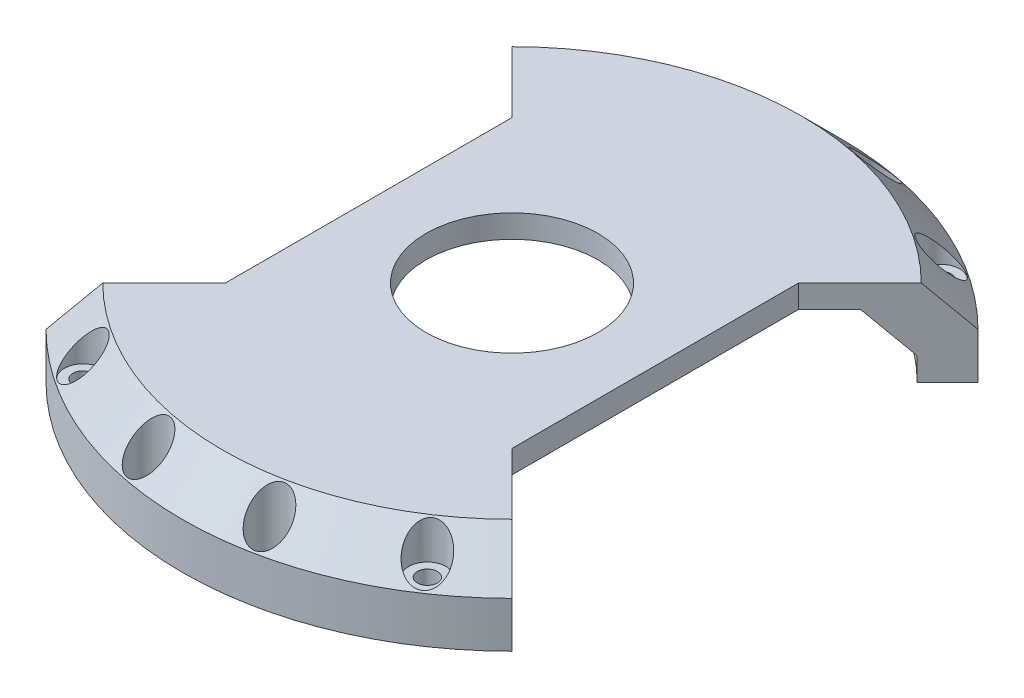
SolidWorks part; units mm, degrees
ref_plane "Front Plane" through (0, 0, 0) normal (0, 0, 1) x (1, 0, 0)
ref_plane "Top Plane" through (0, 0, 0) normal (0, 1, 0) x (1, 0, 0)
ref_plane "Right Plane" through (0, 0, 0) normal (1, 0, 0) x (0, 0, -1)
sketch "Sketch1" plane through (0, 0, 0) normal (0, 1, 0) x (1, 0, 0)
  circle A0 centre (0, 0) radius 57.5
  dimension "D1" = 115
extrude "Boss-Extrude1" add sketch "Sketch1" along normal blind 15
sketch "Sketch2" plane through (0, 0, 0) normal (0, -1, 0) x (1, 0, 0)
  circle A0 centre (0, 0) radius 50
  dimension "D1" = 100
extrude "Cut-Extrude1" cut sketch "Sketch2" against normal blind 11
sketch "Sketch3" plane through (0, 15, 0) normal (0, 1, 0) x (1, 0, 0)
  line L0 (0, 0) -> (0, 54) construction
  line L1 (0, 0) -> (-10.6273, 52.9439) construction
  circle A0 centre (0, 0) radius 54 construction
  circle A13 centre (0, 0) radius 15
  circle A14 centre (-10.6273, 52.9439) radius 1.75
  circle A15 centre (10.4424, 52.9807) radius 1.75
  circle A16 centre (29.9224, 44.9517) radius 1.75
  circle A17 centre (44.8469, 30.0791) radius 1.75
  circle A18 centre (52.9439, 10.6273) radius 1.75
  circle A19 centre (52.9807, -10.4424) radius 1.75
  circle A20 centre (44.9517, -29.9224) radius 1.75
  circle A21 centre (30.0791, -44.8469) radius 1.75
  circle A22 centre (10.6273, -52.9439) radius 1.75
  circle A23 centre (-10.4424, -52.9807) radius 1.75
  circle A24 centre (-29.9224, -44.9517) radius 1.75
  circle A25 centre (-44.8469, -30.0791) radius 1.75
  circle A26 centre (-52.9439, -10.6273) radius 1.75
  circle A27 centre (-52.9807, 10.4424) radius 1.75
  circle A28 centre (-44.9517, 29.9224) radius 1.75
  circle A29 centre (-30.0791, 44.8469) radius 1.75
  point P29 (0, 0)
  point P40 (0, 0)
  dimension "D1" = 108
  dimension "D2" = 11.35
  dimension "D4" = 30
  dimension "D3" = 3.5
extrude "Cut-Extrude2" cut sketch "Sketch3" against normal blind 15
sketch "Sketch4" plane through (0, 15, 0) normal (0, 1, 0) x (1, 0, 0)
  line L0 (25, 25) -> (40.6586, 40.6586)
  line L1 (-25, 25) -> (25, 25) construction
  line L2 (-25, 25) -> (-25, -25) construction
  line L3 (-25, -25) -> (25, -25) construction
  line L4 (25, 25) -> (25, -25)
  line L5 (-25, 25) -> (25, -25) construction
  line L6 (-25, -25) -> (25, 25) construction
  line L7 (25, -25) -> (40.6586, -40.6586)
  circle A0 centre (0, 0) radius 57.5 construction
  arc A1 (40.6586, -40.6586) -> (40.6586, 40.6586) centre (0, 0) ccw
  point P0 (0, 0)
  dimension "D1" = 50
extrude "Cut-Extrude3" cut sketch "Sketch4" against normal blind 15
mirror "Mirror1" about plane through (0, 0, 0) normal (1, 0, 0) of "Cut-Extrude3"
chamfer "Chamfer1" distance 7 angle 45 4 edges at (0, 15, -57.5) (0, 15, 57.5) (0, 11, 50) (0, 11, -50)
sketch "Sketch5" plane through (0, 15, 0) normal (0, 1, 0) x (1, 0, 0)
  line L0 (0, 0) -> (-10.6273, 52.9439) construction
  circle A0 centre (0, 0) radius 54 construction
  circle A1 centre (-10.6273, 52.9439) radius 3.25
  circle A2 centre (10.4424, 52.9807) radius 3.25
  circle A3 centre (29.9224, 44.9517) radius 3.25
  circle A4 centre (44.8469, 30.0791) radius 3.25
  circle A5 centre (52.9439, 10.6273) radius 3.25
  circle A6 centre (52.9807, -10.4424) radius 3.25
  circle A7 centre (44.9517, -29.9224) radius 3.25
  circle A8 centre (30.0791, -44.8469) radius 3.25
  circle A9 centre (10.6273, -52.9439) radius 3.25
  circle A10 centre (-10.4424, -52.9807) radius 3.25
  circle A11 centre (-29.9224, -44.9517) radius 3.25
  circle A12 centre (-44.8469, -30.0791) radius 3.25
  circle A13 centre (-52.9439, -10.6273) radius 3.25
  circle A14 centre (-52.9807, 10.4424) radius 3.25
  circle A15 centre (-44.9517, 29.9224) radius 3.25
  circle A16 centre (-30.0791, 44.8469) radius 3.25
  point P32 (0, 0)
  point P41 (0, 0)
  dimension "D1" = 6.5
extrude "Cut-Extrude4" cut sketch "Sketch5" against normal blind 7
sketch "Sketch6" plane through (0, 15, 0) normal (0, 1, 0) x (1, 0, 0)
  circle A0 centre (-10.6273, 52.9439) radius 3.25
  circle A1 centre (10.4424, 52.9807) radius 3.25
  circle A2 centre (-10.4424, -52.9807) radius 3.25
  circle A3 centre (10.6273, -52.9439) radius 3.25
extrude "Cut-Extrude5" cut sketch "Sketch6" against normal blind 55
